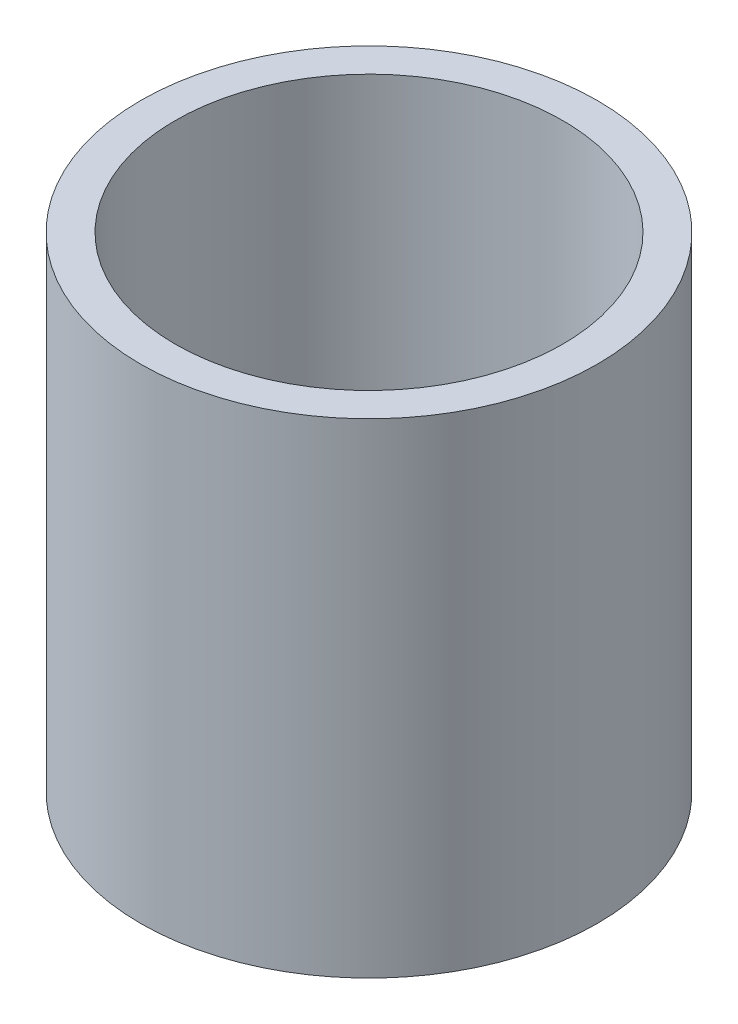
SolidWorks part; units mm, degrees
ref_plane "Front Plane" through (0, 0, 0) normal (0, 0, 1) x (1, 0, 0)
ref_plane "Top Plane" through (0, 0, 0) normal (0, 1, 0) x (1, 0, 0)
ref_plane "Right Plane" through (0, 0, 0) normal (1, 0, 0) x (0, 0, -1)
sketch "Sketch1" plane through (0, 0, 0) normal (0, 1, 0) x (1, 0, 0)
  circle A0 centre (0, 0) radius 825
  dimension "D1" = 1650
extrude "Boss-Extrude1" add sketch "Sketch1" along normal mid plane 1750
sketch "Sketch2" plane through (0, 0, 0) normal (0, 1, 0) x (1, 0, 0)
  circle A0 centre (0, 0) radius 700
  dimension "D1" = 1400
extrude "Cut-Extrude1" cut sketch "Sketch2" against normal through all both and the other way through all
